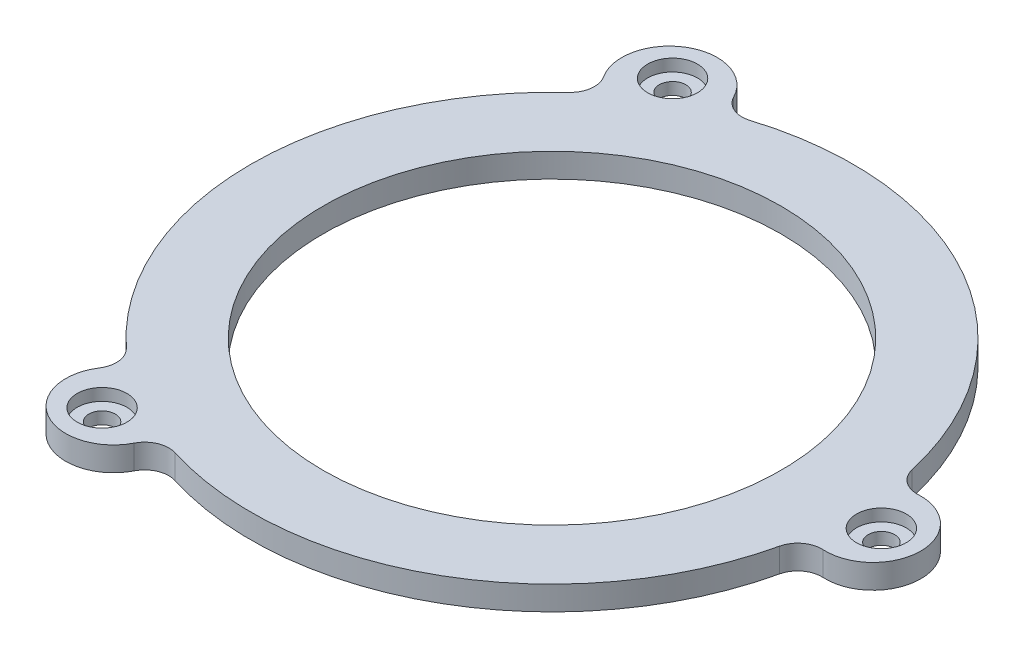
SolidWorks part; units mm, degrees
ref_plane "Front Plane" through (0, 0, 0) normal (0, 0, 1) x (1, 0, 0)
ref_plane "Top Plane" through (0, 0, 0) normal (0, 1, 0) x (1, 0, 0)
ref_plane "Right Plane" through (0, 0, 0) normal (1, 0, 0) x (0, 0, -1)
sketch "Sketch1" plane through (0, 0, 0) normal (0, 1, 0) x (1, 0, 0)
  circle A0 centre (0, 0) radius 28.5
  circle A1 centre (0, 0) radius 37.5
  dimension "D1" = 57
  dimension "D2" = 75
extrude "Boss-Extrude1" add sketch "Sketch1" along normal blind 3
sketch "Sketch3" plane through (0, 3, 0) normal (0, 1, 0) x (1, 0, 0)
  line L1 (0, 0) -> (44, 0) construction
  line L2 (0, 0) -> (37.1351, -5.219) construction
  line L3 (0, 0) -> (37.1351, 5.219) construction
  arc A1 (37.1351, 5.219) -> (37.1351, -5.219) centre (39.9644, 0) cw
  circle A4 centre (0, 0) radius 37.5 construction
  arc A5 (37.1351, 5.219) -> (37.1351, -5.219) centre (0, 0) cw
  arc A11 (-14.0477, -34.7694) -> (-23.0873, -29.5504) centre (-19.9822, -34.6102) cw
  arc A12 (-14.0477, -34.7694) -> (-23.0873, -29.5504) centre (0, 0) cw
  arc A13 (-23.0873, 29.5504) -> (-14.0477, 34.7694) centre (-19.9822, 34.6102) cw
  arc A14 (-23.0873, 29.5504) -> (-14.0477, 34.7694) centre (0, 0) cw
  point P17 (0, 0)
  dimension "D1" = 8
  dimension "D2" = 8
  dimension "D3" = 3
extrude "Boss-Extrude2" add sketch "Sketch3" against normal blind 3
sketch "Sketch6" plane through (0, 3, 0) normal (0, 1, 0) x (1, 0, 0)
  line L0 (0, 0) -> (41, 0) construction
  circle A0 centre (41, 0) radius 1.65
  circle A3 centre (-20.5, -35.507) radius 1.65
  circle A4 centre (-20.5, 35.507) radius 1.65
  point P11 (0, 0)
  dimension "D1" = 3.3
  dimension "D2" = 41
extrude "Cut-Extrude2" cut sketch "Sketch6" against normal blind 10
sketch "Sketch7" plane through (0, 3, 0) normal (0, 1, 0) x (1, 0, 0)
  circle A0 centre (41, 0) radius 3.1
  circle A5 centre (-20.5, -35.507) radius 3.1
  circle A6 centre (-20.5, 35.507) radius 3.1
  point P10 (1, 0.5774)
  point P11 (0.75, 0.433)
  point P16 (0, 0)
  dimension "D1" = 6.2
  dimension "D3" = 3
extrude "Cut-Extrude3" cut sketch "Sketch7" against normal blind 1.5 contours A0 | A5 | A6
fillet "Fillet1" radius 3 6 edges at (37.1351, 1.5, 5.219) (-14.0477, 1.5, 34.7694) (-23.0873, 1.5, 29.5504) (-23.0873, 1.5, -29.5504) (-14.0477, 1.5, -34.7694) (37.1351, 1.5, -5.219)
